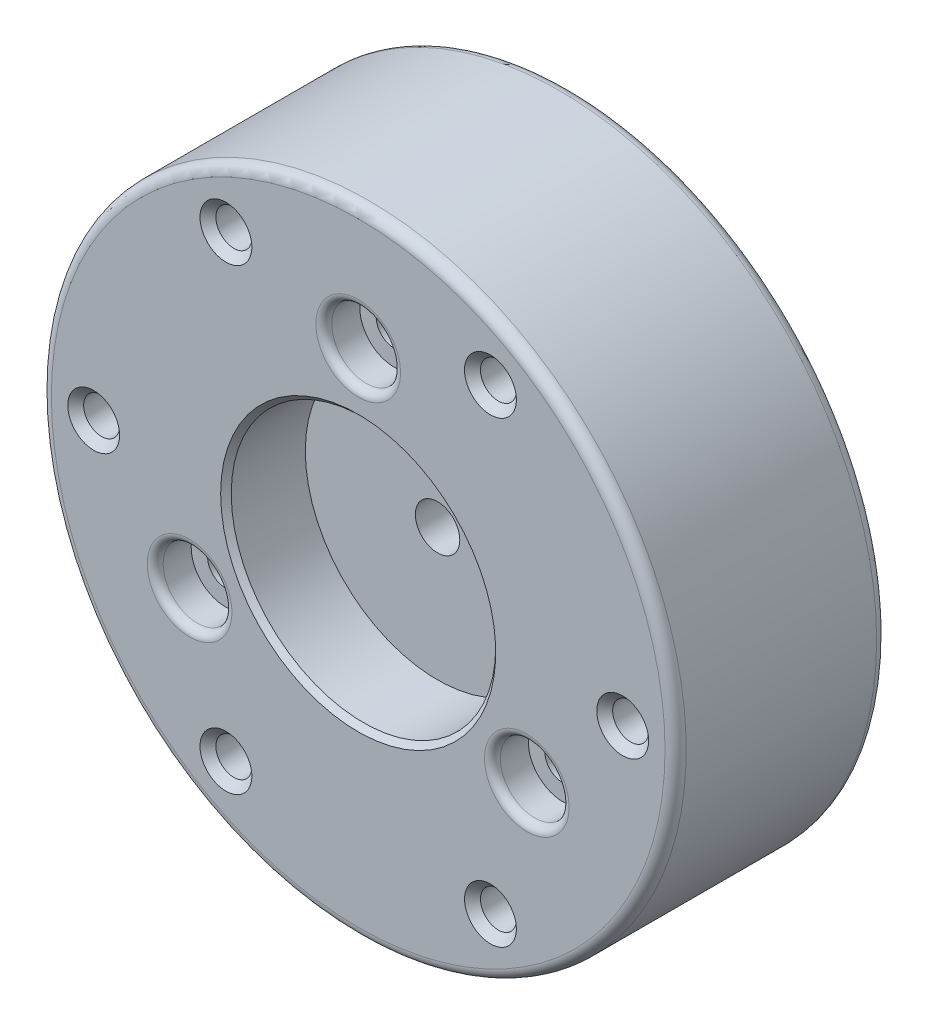
SolidWorks part; units mm, degrees
ref_plane "Ebene vorne" through (0, 0, 0) normal (0, 0, 1) x (1, 0, 0)
ref_plane "Ebene oben" through (0, 0, 0) normal (0, 1, 0) x (1, 0, 0)
ref_plane "Ebene rechts" through (0, 0, 0) normal (1, 0, 0) x (0, 0, -1)
sketch "Skizze1" plane through (0, 0, 0) normal (0, 1, 0) x (1, 0, 0)
  line L0 (0, 0) -> (0, -12.5)
  line L1 (0, -12.5) -> (12.5, -12.5)
  line L2 (12.5, -12.5) -> (12.5, -20)
  line L3 (12.5, -20) -> (30, -20)
  line L4 (30, -20) -> (30, 0)
  line L5 (30, 0) -> (0, 0)
  point P7 (30, -10)
  dimension "D1" = 12.5
  dimension "D2" = 30
  dimension "D3" = 20
  dimension "D4" = 7.5
revolve "Rotation1" add sketch "Skizze1" angle 360 about L0
sketch "Skizze2" plane through (0, 0, 20) normal (0, 0, 1) x (1, 0, 0)
  circle A0 centre (0, 0) radius 18.4 construction
  point P3 (0, 18.4)
  dimension "D1" = 36.8
hole_wizard "Stirnsenkung für M3 Zylinderschraube mit Innensechskant1" positions "Skizze3" profile "Skizze4" counterbore size "M3" standard "DIN"
sketch "Skizze3" plane through (0, 0, 20) normal (0, 0, 1) x (1, 0, 0)
  point P0 (0, 18.4)
sketch "Skizze4" plane through (0, 18.4, 20) normal (1, 0, 0) x (0, -1, 0)
  line L0 (0, 0) -> (0, 21.0205)
  line L1 (0, 21.0205) -> (1.7, 19.999)
  line L2 (1.7, 19.999) -> (1.7, 3.4)
  line L3 (1.7, 3.4) -> (3.25, 3.4)
  line L4 (3.25, 3.4) -> (3.25, 0)
  line L5 (3.25, 0) -> (0, 0)
  line L10 (0, 21.0205) -> (-1.7, 19.999) construction
  line L11 (0, -6.35) -> (0, 107.95) construction
  dimension "Bohrerdurchmesser" = 3.4
  dimension "Bohrungstiefe" = 19.999
  dimension "Senkdurchmesser2" = 6.5
  dimension "Senktiefe2" = 3.4
  dimension "Spitzenwinkel" = 118
fillet "Verrundung1" radius 0.75 1 edges at (3.25, 18.4, 20)
chamfer "Fase1" distance 0.75 angle 45 1 edges at (1.7, 18.4, 0)
pattern_circular "Kreismuster1" count 3 every 120 about axis through (0, 0, 0) along (0, 0, 1) of "Stirnsenkung für M3 Zylinderschraube mit Innensechskant1", "Verrundung1", "Fase1"
sketch "Skizze5" plane through (0, 0, 0) normal (0, 0, -1) x (-1, 0, 0)
  line L0 (0, 25) -> (0, 0) construction
  line L1 (0, 0) -> (12.5, 21.6506) construction
  circle A0 centre (0, 0) radius 25 construction
  point P3 (12.5, 21.6506)
  dimension "D1" = 50
  dimension "D2" = 30
hole_wizard "Stirnsenkung für M3 Zylinderschraube mit Innensechskant2" positions "Skizze6" profile "Skizze7" counterbore size "M3" standard "DIN"
sketch "Skizze6" plane through (0, 0, 0) normal (0, 0, -1) x (-1, 0, 0)
  point P0 (12.5, 21.6506)
sketch "Skizze7" plane through (-12.5, 21.6506, 0) normal (1, 0, 0) x (0, 1, 0)
  line L0 (0, 0) -> (0, 21.0205)
  line L1 (0, 21.0205) -> (1.7, 19.999)
  line L2 (1.7, 19.999) -> (1.7, 3.4)
  line L3 (1.7, 3.4) -> (3.25, 3.4)
  line L4 (3.25, 3.4) -> (3.25, 0)
  line L5 (3.25, 0) -> (0, 0)
  line L10 (0, 21.0205) -> (-1.7, 19.999) construction
  line L11 (0, -6.35) -> (0, 107.95) construction
  dimension "Bohrerdurchmesser" = 3.4
  dimension "Bohrungstiefe" = 19.999
  dimension "Senkdurchmesser2" = 6.5
  dimension "Senktiefe2" = 3.4
  dimension "Spitzenwinkel" = 118
fillet "Verrundung2" radius 0.75 1 edges at (-15.75, 21.6506, 0)
chamfer "Fase2" distance 0.75 angle 45 1 edges at (-14.2, 21.6506, 20)
pattern_circular "Kreismuster2" count 6 every 60 about axis through (0, 0, 0) along (0, 0, 1) of "Stirnsenkung für M3 Zylinderschraube mit Innensechskant2", "Verrundung2", "Fase2"
sketch "Skizze8" plane through (0, 0, 12.5) normal (0, 0, 1) x (1, 0, 0)
  circle A0 centre (0, 0) radius 2.25
  dimension "D1" = 4.5
extrude "Schnitt-Linear austragen1" [suppressed] cut sketch "Skizze8" against normal up to surface (15 mm away)
sketch "Skizze9" plane through (0, 0, 0) normal (0, 0, -1) x (-1, 0, 0)
  circle A0 centre (0, 0) radius 3.375
  dimension "D1" = 6.75
extrude "Schnitt-Linear austragen2" cut sketch "Skizze9" against normal blind 7.5
chamfer "Fase3" distance 0.5 angle 45 1 edges at (-12.5, 0, 20)
chamfer "Fase4" distance 1 angle 45 1 edges at (-3.375, 0, 0)
fillet "Verrundung3" radius 1 2 edges at (-30, 0, 0) (-30, 0, 20)
hole_wizard "M5 Gewindebohrung1" positions "Skizze10" profile "Skizze12" tap size "M5" standard "DIN"
sketch "Skizze10" plane through (0, 0, 12.5) normal (0, 0, 1) x (1, 0, 0)
  point P0 (0, 0)
sketch "Skizze12" plane through (0, 0, 12.5) normal (1, 0, 0) x (0, -1, 0)
  line L0 (0, 0) -> (0, 6.2608)
  line L1 (0, 6.2608) -> (2.1, 4.999)
  line L2 (2.1, 4.999) -> (2.1, 0)
  line L5 (2.1, 0) -> (0, 0)
  line L10 (0, 6.2608) -> (-2.1, 4.999) construction
  line L11 (0, -6.35) -> (0, 107.95) construction
  dimension "Bohrerdurchmesser" = 4.2
  dimension "Bohrungstiefe" = 4.999
  dimension "Spitzenwinkel" = 118
cosmetic thread "Bohrungsgewinde1" parameters "D1"=10, "D2"=5
